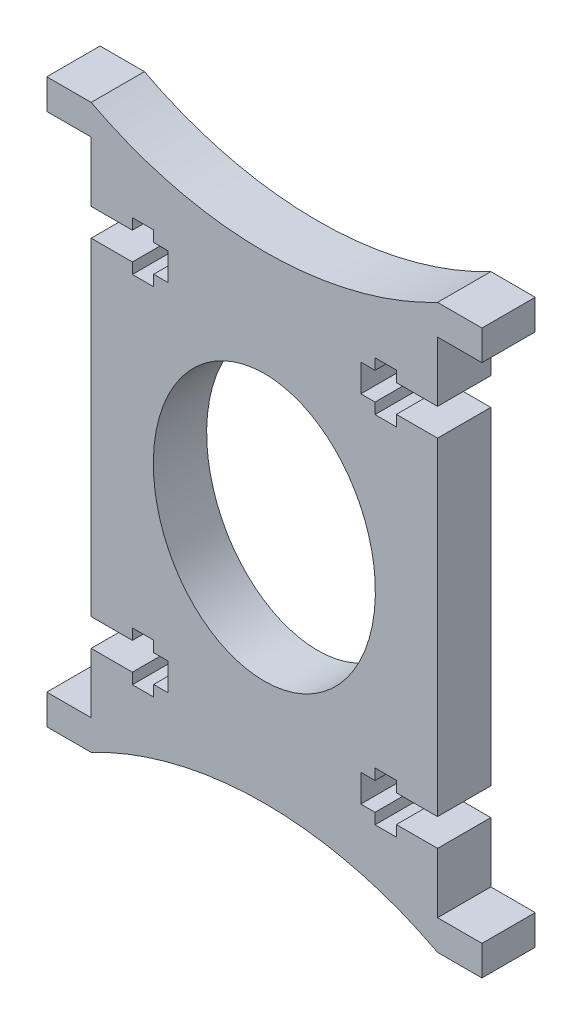
SolidWorks part; units mm, degrees
material "Acrylic (Medium-high impact)"
ref_plane "Front Plane" through (0, 0, 0) normal (0, 0, 1) x (1, 0, 0)
ref_plane "Top Plane" through (0, 0, 0) normal (0, 1, 0) x (1, 0, 0)
ref_plane "Right Plane" through (0, 0, 0) normal (1, 0, 0) x (0, 0, -1)
sketch "Sketch1" plane through (0, 0, 0) normal (0, 0, 1) x (1, 0, 0)
  line L0 (741.0185, 459.4261) -> (702.0185, 459.4261) construction
  line L1 (736.3803, 439.4261) -> (741.0185, 439.4261) construction
  line L2 (736.3803, 439.4261) -> (736.3803, 437.8782) construction
  line L3 (736.3803, 440.9739) -> (736.3803, 439.4261) construction
  line L4 (735.1803, 436.6538) -> (735.1803, 439.4261) construction
  line L5 (732.3803, 439.4261) -> (741.0185, 439.4261) construction
  line L6 (735.1803, 442.1983) -> (735.1803, 439.4261) construction
  line L7 (733.9803, 436.6538) -> (736.3803, 436.6538)
  line L8 (702.0185, 459.4261) -> (702.0185, 440.9739)
  line L9 (707.8567, 442.1983) -> (707.8567, 439.4261) construction
  line L10 (733.9803, 442.1983) -> (736.3803, 442.1983)
  line L11 (732.3803, 440.9739) -> (732.3803, 437.8782)
  line L12 (741.0185, 437.8782) -> (741.0185, 431.1161)
  line L13 (741.0185, 437.8782) -> (736.3803, 437.8782)
  line L14 (736.3803, 440.9739) -> (741.0185, 440.9739)
  line L15 (746.0185, 427.7361) -> (746.0185, 431.1161)
  line L16 (741.0185, 427.7361) -> (746.0185, 427.7361)
  line L17 (710.6567, 439.4261) -> (702.0185, 439.4261) construction
  line L18 (709.0567, 436.6538) -> (709.0567, 437.8782)
  line L19 (709.0567, 440.9739) -> (710.6567, 440.9739)
  line L20 (709.0567, 437.8782) -> (710.6567, 437.8782)
  line L21 (709.0567, 440.9739) -> (709.0567, 442.1983)
  line L22 (707.8567, 436.6538) -> (707.8567, 439.4261) construction
  line L23 (706.6567, 436.6538) -> (706.6567, 437.8782)
  line L24 (706.6567, 440.9739) -> (706.6567, 442.1983)
  line L25 (706.6567, 440.9739) -> (706.6567, 439.4261) construction
  line L26 (706.6567, 439.4261) -> (706.6567, 437.8782) construction
  line L27 (697.0185, 431.1161) -> (702.0185, 431.1161)
  line L28 (702.0185, 427.7361) -> (697.0185, 427.7361)
  line L29 (697.0185, 427.7361) -> (697.0185, 431.1161)
  line L30 (706.6567, 440.9739) -> (702.0185, 440.9739)
  line L31 (702.0185, 437.8782) -> (706.6567, 437.8782)
  line L32 (702.0185, 437.8782) -> (702.0185, 431.1161)
  line L33 (706.6567, 439.4261) -> (702.0185, 439.4261) construction
  line L34 (710.6567, 440.9739) -> (710.6567, 437.8782)
  line L35 (746.0185, 431.1161) -> (741.0185, 431.1161)
  line L36 (736.3803, 440.9739) -> (736.3803, 442.1983)
  line L37 (736.3803, 436.6538) -> (736.3803, 437.8782)
  line L38 (733.9803, 440.9739) -> (733.9803, 442.1983)
  line L39 (733.9803, 437.8782) -> (732.3803, 437.8782)
  line L40 (733.9803, 440.9739) -> (732.3803, 440.9739)
  line L41 (733.9803, 436.6538) -> (733.9803, 437.8782)
  line L42 (741.0185, 459.4261) -> (741.0185, 440.9739)
  line L43 (706.6567, 479.4261) -> (702.0185, 479.4261) construction
  line L44 (709.0567, 442.1983) -> (706.6567, 442.1983)
  line L45 (706.6567, 479.4261) -> (706.6567, 480.9739) construction
  line L46 (706.6567, 477.8782) -> (706.6567, 479.4261) construction
  line L47 (707.8567, 482.1983) -> (707.8567, 479.4261) construction
  line L48 (710.6567, 479.4261) -> (702.0185, 479.4261) construction
  line L49 (707.8567, 476.6538) -> (707.8567, 479.4261) construction
  line L50 (735.1803, 476.6538) -> (735.1803, 479.4261) construction
  line L51 (732.3803, 479.4261) -> (741.0185, 479.4261) construction
  line L52 (735.1803, 482.1983) -> (735.1803, 479.4261) construction
  line L53 (736.3803, 477.8782) -> (736.3803, 479.4261) construction
  line L54 (736.3803, 479.4261) -> (736.3803, 480.9739) construction
  line L55 (736.3803, 479.4261) -> (741.0185, 479.4261) construction
  line L56 (709.0567, 482.1983) -> (706.6567, 482.1983)
  line L57 (709.0567, 476.6538) -> (706.6567, 476.6538)
  line L58 (741.0185, 459.4261) -> (741.0185, 477.8782)
  line L59 (733.9803, 482.1983) -> (733.9803, 480.9739)
  line L60 (721.5185, -540.5691) -> (721.5185, 49459.4309) construction
  line L61 (709.0567, 436.6538) -> (706.6567, 436.6538)
  line L62 (733.9803, 477.8782) -> (732.3803, 477.8782)
  line L63 (733.9803, 480.9739) -> (732.3803, 480.9739)
  line L64 (733.9803, 477.8782) -> (733.9803, 476.6538)
  line L65 (736.3803, 482.1983) -> (736.3803, 480.9739)
  line L66 (736.3803, 477.8782) -> (736.3803, 476.6538)
  line L67 (746.0185, 487.7361) -> (741.0185, 487.7361)
  line L68 (710.6567, 477.8782) -> (710.6567, 480.9739)
  line L69 (702.0185, 480.9739) -> (702.0185, 487.7361)
  line L70 (702.0185, 480.9739) -> (706.6567, 480.9739)
  line L71 (706.6567, 477.8782) -> (702.0185, 477.8782)
  line L72 (697.0185, 491.1161) -> (697.0185, 487.7361)
  line L73 (702.0185, 491.1161) -> (697.0185, 491.1161)
  line L74 (697.0185, 487.7361) -> (702.0185, 487.7361)
  line L75 (706.6567, 477.8782) -> (706.6567, 476.6538)
  line L76 (706.6567, 482.1983) -> (706.6567, 480.9739)
  line L77 (709.0567, 477.8782) -> (709.0567, 476.6538)
  line L78 (709.0567, 480.9739) -> (710.6567, 480.9739)
  line L79 (709.0567, 477.8782) -> (710.6567, 477.8782)
  line L80 (709.0567, 482.1983) -> (709.0567, 480.9739)
  line L81 (741.0185, 491.1161) -> (746.0185, 491.1161)
  line L82 (746.0185, 491.1161) -> (746.0185, 487.7361)
  line L83 (736.3803, 477.8782) -> (741.0185, 477.8782)
  line L84 (741.0185, 480.9739) -> (736.3803, 480.9739)
  line L85 (741.0185, 480.9739) -> (741.0185, 487.7361)
  line L86 (732.3803, 477.8782) -> (732.3803, 480.9739)
  line L87 (733.9803, 476.6538) -> (736.3803, 476.6538)
  line L88 (702.0185, 459.4261) -> (702.0185, 477.8782)
  line L89 (733.9803, 482.1983) -> (736.3803, 482.1983)
  line L90 (721.5185, 459.4261) -> (708.0185, 459.4261) construction
  line L91 (702.0185, 480.9739) -> (702.0185, 477.8782) construction
  line L92 (702.0185, 487.7361) -> (702.0185, 491.1161) construction
  line L93 (702.0185, 431.1161) -> (702.0185, 427.7361) construction
  line L94 (702.0185, 491.1161) -> (741.0185, 491.1161) construction
  line L95 (702.0185, 427.7361) -> (741.0185, 427.7361) construction
  line L96 (741.0185, 480.9739) -> (741.0185, 477.8782) construction
  line L97 (741.0185, 440.9739) -> (741.0185, 437.8782) construction
  arc A0 (702.0185, 491.1161) -> (741.0185, 491.1161) centre (721.5185, 528.3149) ccw
  arc A1 (702.0185, 427.7361) -> (741.0185, 427.7361) centre (721.5185, 390.5373) cw
  ellipse E0 centre (721.5185, 459.4261) end of major axis (721.5185, 474.4261) minor radius 12.5
  point P30 (721.5185, 474.4261)
  point P38 (721.5185, 459.4261)
  point P102 (702.0185, 489.4261)
  point P103 (702.0185, 429.4261)
  point P105 (721.5185, 444.4261)
  dimension "D9" = 42
  dimension "D1" = 60
  dimension "D2" = 3.0957
  dimension "D3" = 3.38
  dimension "D4" = 10
  dimension "D5" = 1.6
  dimension "D6" = 39
  dimension "D7" = 2.4
  dimension "D8" = 1.2244
  dimension "D10" = 5
  dimension "D11" = 15
  dimension "D12" = 25
  dimension "D15" = 4.6382
extrude "Boss-Extrude1" add sketch "Sketch1" along normal blind 6
